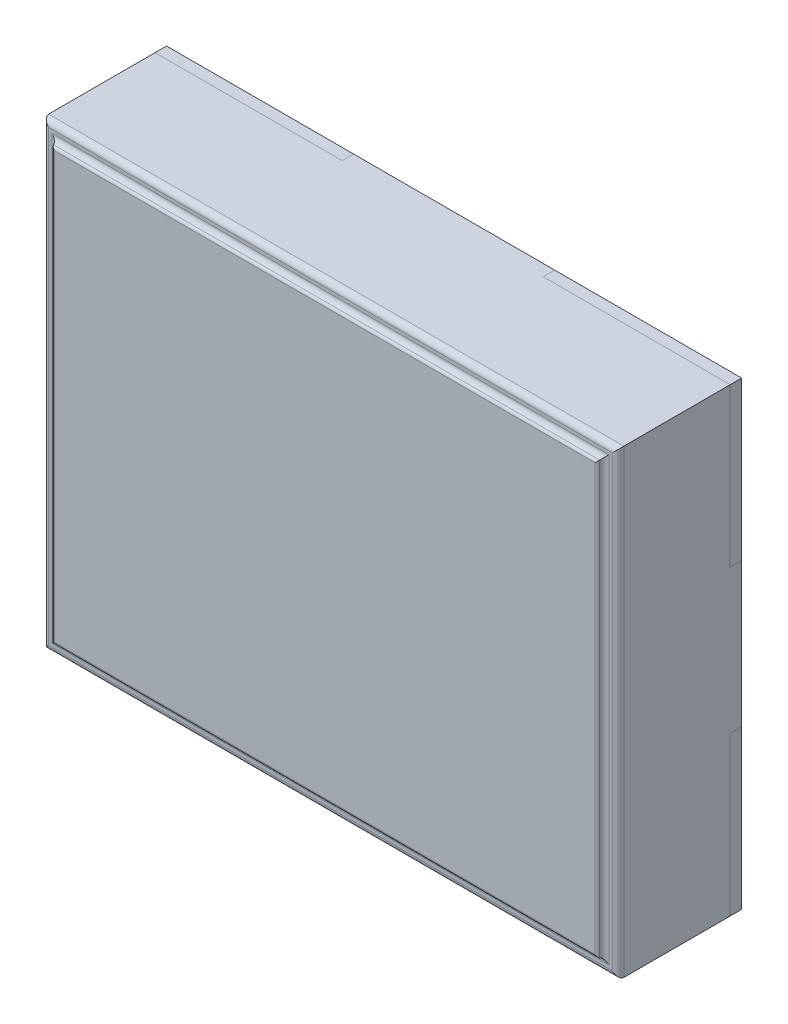
SolidWorks part; units mm, degrees
ref_plane "Front Plane" through (0, 0, 0) normal (0, 0, 1) x (1, 0, 0)
ref_plane "Top Plane" through (0, 0, 0) normal (0, 1, 0) x (1, 0, 0)
ref_plane "Right Plane" through (0, 0, 0) normal (1, 0, 0) x (0, 0, -1)
sketch "Sketch1" plane through (0, 0, 0) normal (0, 0, 1) x (1, 0, 0)
  line L1 (-1, -0.8) -> (1, -0.8)
  line L2 (-1, -0.8) -> (-1, 0.8)
  line L3 (-1, 0.8) -> (1, 0.8)
  line L4 (1, -0.8) -> (1, 0.8)
  line L5 (-1, -0.8) -> (1, 0.8) construction
  line L6 (-1, 0.8) -> (1, -0.8) construction
  line L7 (-1, 0.25) -> (-0.35, 0.25)
  line L8 (-1, 0.25) -> (-1, 0.8)
  line L9 (-1, 0.8) -> (-0.35, 0.8)
  line L10 (-0.35, 0.25) -> (-0.35, 0.8)
  line L11 (0.35, 0.8) -> (1, 0.8)
  line L12 (0.35, 0.8) -> (0.35, 0.25)
  line L13 (0.35, 0.25) -> (1, 0.25)
  line L14 (1, 0.8) -> (1, 0.25)
  line L15 (0.35, -0.25) -> (1, -0.25)
  line L16 (0.35, -0.25) -> (0.35, -0.8)
  line L17 (0.35, -0.8) -> (1, -0.8)
  line L18 (1, -0.25) -> (1, -0.8)
  line L19 (-1, -0.25) -> (-0.35, -0.25)
  line L20 (-1, -0.25) -> (-1, -0.8)
  line L21 (-1, -0.8) -> (-0.35, -0.8)
  line L22 (-0.35, -0.25) -> (-0.35, -0.8)
  point P0 (0, 0)
  point P15 (0, 0)
  point P22 (1, -0.525)
  point P23 (0, 0)
  dimension "D1" = 2
  dimension "D2" = 1.6
  dimension "D3" = 0.65
  dimension "D4" = 0.55
  dimension "D5" = 0.65
  dimension "D6" = 0.55
  dimension "D7" = 0.55
  dimension "D8" = 0.65
  dimension "D9" = 0.55
  dimension "D10" = 0.65
  dimension "D11" = 0.7
  dimension "D12" = 0.7
  dimension "D13" = 0.5
extrude "Boss-Extrude1" add sketch "Sketch1" along normal blind 0.04 contours L7 L10 L3 L2 | L12 L13 L4 L3 | L15 L16 L1 L4 | L22 L19 L2 L1 region at (-0.675, -0.525, 0) region at (0.675, -0.525, 0) region at (-0.675, 0.525, 0) region at (0.675, 0.525, 0)
extrude "Boss-Extrude2" add sketch "Sketch1<3>" along normal blind 0.43 separate body contours L19 L22 L1 L16 L15 L4 L13 L12 L3 L10 L7 L2 region at (0, 0, 0)
sketch "Sketch1<3>" plane through (0, 0, 0) normal (0, 0, 1) x (1, 0, 0) same geometry as "Sketch1"
extrude "Boss-Extrude3" add sketch "Sketch1<4>" along normal blind 0.39 from offset 0.04 separate body contours L12 L13 L4 L3 | L7 L10 L3 L2 | L15 L16 L1 L4 | L22 L19 L2 L1 region at (-0.675, -0.525, 0) region at (0.675, -0.525, 0) region at (-0.675, 0.525, 0) region at (0.675, 0.525, 0)
sketch "Sketch1<4>" plane through (0, 0, 0) normal (0, 0, 1) x (1, 0, 0) same geometry as "Sketch1"
sketch "Sketch2" plane through (0, 0, 0.43) normal (0, 0, 1) x (1, 0, 0)
  line L1 (-0.95, -0.75) -> (0.95, -0.75)
  line L2 (-0.95, -0.75) -> (-0.95, 0.75)
  line L3 (-0.95, 0.75) -> (0.95, 0.75)
  line L4 (0.95, -0.75) -> (0.95, 0.75)
  line L5 (-0.95, -0.75) -> (0.95, 0.75) construction
  line L6 (-0.95, 0.75) -> (0.95, -0.75) construction
  point P0 (0, 0)
  dimension "D1" = 1.9
  dimension "D2" = 1.5
extrude "Boss-Extrude4" add sketch "Sketch2" along normal blind 0.02
fillet "Fillet1" radius 0.01 4 edges at (0, -0.75, 0.45) (-0.95, 0, 0.45) (0, 0.75, 0.45) (0.95, 0, 0.45)
fillet "Fillet4" radius 0.02 8 edges at (-0.95, 0, 0.43) (0, -0.75, 0.43) (0.95, 0, 0.43) (0, 0.75, 0.43) (0, 0.8, 0.43) (1, 0, 0.43) (0, -0.8, 0.43) (-1, 0, 0.43)
